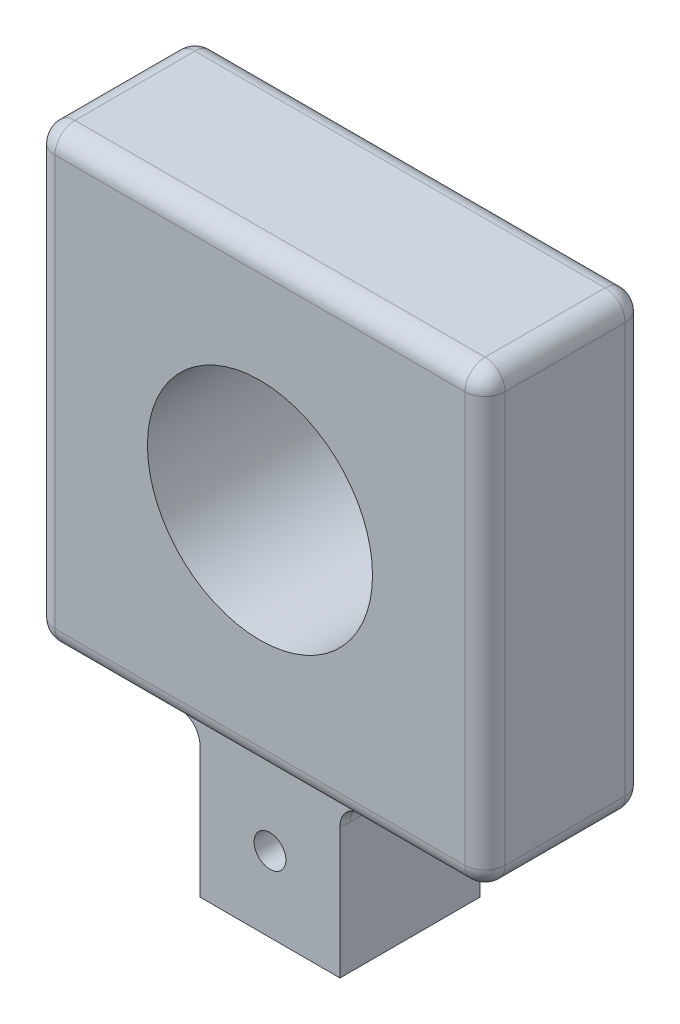
SolidWorks part; units mm, degrees
ref_plane "Front Plane" through (0, 0, 0) normal (0, 0, 1) x (1, 0, 0)
ref_plane "Top Plane" through (0, 0, 0) normal (0, 1, 0) x (1, 0, 0)
ref_plane "Right Plane" through (0, 0, 0) normal (1, 0, 0) x (0, 0, -1)
sketch "Sketch1" plane through (0, 0, 0) normal (0, 1, 0) x (1, 0, 0)
  line L1 (-8.89, -8.89) -> (8.89, -8.89)
  line L2 (-8.89, -8.89) -> (-8.89, 8.89)
  line L3 (-8.89, 8.89) -> (8.89, 8.89)
  line L4 (8.89, -8.89) -> (8.89, 8.89)
  line L5 (-8.89, -8.89) -> (8.89, 8.89) construction
  line L6 (-8.89, 8.89) -> (8.89, -8.89) construction
  point P0 (0, 0)
  dimension "D1" = 17.78
  dimension "D2" = 17.78
extrude "Boss-Extrude1" add sketch "Sketch1" along normal blind 12.7 and the other way blind 6.35
sketch "Sketch2" plane through (0, 12.7, 0) normal (0, 1, 0) x (1, 0, 0)
  line L1 (-28.575, -10.16) -> (28.575, -10.16)
  line L2 (-28.575, -10.16) -> (-28.575, 10.16)
  line L3 (-28.575, 10.16) -> (28.575, 10.16)
  line L4 (28.575, -10.16) -> (28.575, 10.16)
  line L5 (-28.575, -10.16) -> (28.575, 10.16) construction
  line L6 (-28.575, 10.16) -> (28.575, -10.16) construction
  point P0 (0, 0)
  dimension "D1" = 57.15
  dimension "D2" = 20.32
extrude "Boss-Extrude2" add sketch "Sketch2" along normal blind 57.15
sketch "Sketch3" plane through (0, 0, 10.16) normal (0, 0, 1) x (1, 0, 0)
  line L0 (-28.575, 69.85) -> (28.575, 69.85) construction
  line L1 (28.575, 69.85) -> (28.575, 12.7) construction
  circle A0 centre (0, 41.275) radius 14.2875
  dimension "D1" = 28.575
  dimension "D2" = 28.575
  dimension "D3" = 28.575
extrude "Cut-Extrude1" cut sketch "Sketch3" against normal through all
fillet "Fillet1" radius 2.54 12 edges at (28.575, 69.85, 0) (28.575, 12.7, 0) (-28.575, 69.85, 0) (-28.575, 12.7, 0) (28.575, 41.275, -10.16) (0, 69.85, -10.16) (-28.575, 41.275, -10.16) (0, 12.7, -10.16) (-28.575, 41.275, 10.16) (0, 69.85, 10.16) (28.575, 41.275, 10.16) (0, 12.7, 10.16)
sketch "Sketch4" plane through (0, 0, -8.89) normal (0, 0, -1) x (-1, 0, 0)
  line L0 (-8.89, -6.35) -> (8.89, -6.35) construction
  line L1 (-8.89, -6.35) -> (-8.89, 13.0403) construction
  circle A0 centre (0, 3.175) radius 2.0193
  dimension "D1" = 4.0386
  dimension "D2" = 9.525
  dimension "D3" = 8.89
extrude "Cut-Extrude2" cut sketch "Sketch4" against normal through all
fillet "Fillet2" radius 2.54 6 edges at (-8.89, 12.7865, -8.2774) (-8.89, 12.7865, 8.2774) (8.89, 12.7865, 8.2774) (8.89, 12.7865, -8.2774) (-8.89, 12.7, 0) (8.89, 12.7, 0)
